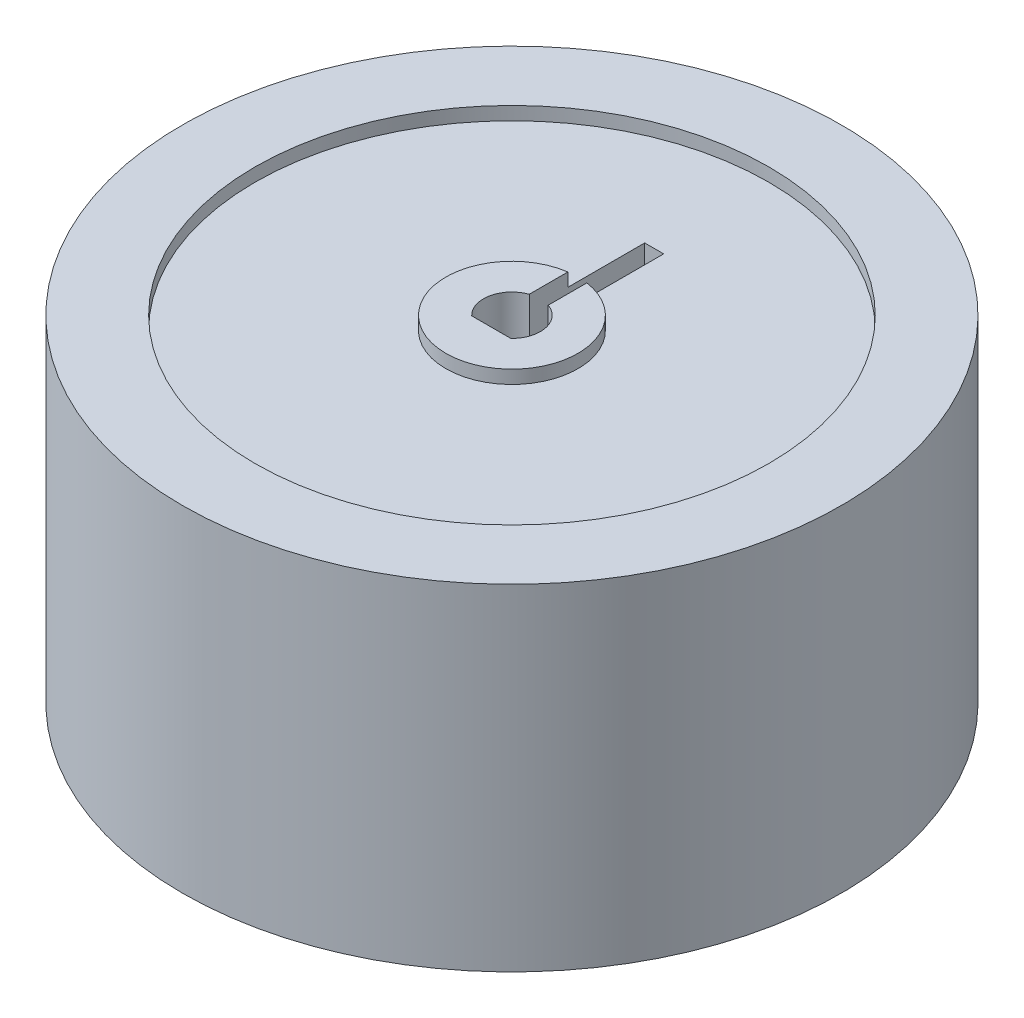
SolidWorks part; units mm, degrees
ref_plane "Front Plane" through (0, 0, 0) normal (0, 0, 1) x (1, 0, 0)
ref_plane "Top Plane" through (0, 0, 0) normal (0, 1, 0) x (1, 0, 0)
ref_plane "Right Plane" through (0, 0, 0) normal (1, 0, 0) x (0, 0, -1)
sketch "Sketch1" plane through (0, 0, 0) normal (0, 1, 0) x (1, 0, 0)
  circle A1 centre (0, 0) radius 17.375
extrude "Boss-Extrude1" add sketch "Sketch1" along normal blind 17.7
sketch "Sketch3" plane through (0, 17.7, 0) normal (0, 1, 0) x (1, 0, 0)
  line L0 (0, 17.375) -> (0, 13.545) construction
  circle A0 centre (0, 0) radius 17.375 construction
  circle A1 centre (0, 0) radius 13.545
extrude "Cut-Extrude1" cut sketch "Sketch3" against normal blind 0.7
sketch "Sketch4" plane through (0, 17, 0) normal (0, 1, 0) x (1, 0, 0)
  line L0 (0, 13.545) -> (0, 3.485) construction
  circle A0 centre (0, 0) radius 13.545 construction
  circle A1 centre (0, 0) radius 13.545 construction
  circle A2 centre (0, 0) radius 3.485
extrude "Boss-Extrude2" add sketch "Sketch4" along normal blind 0.7
sketch "Sketch5" plane through (0, 17.7, 0) normal (0, 1, 0) x (1, 0, 0)
  line L0 (-1.0305, -1.09) -> (1.0305, -1.09)
  arc A1 (-1.0305, -1.09) -> (1.0305, -1.09) centre (0, 0) cw
extrude "Cut-Extrude2" cut sketch "Sketch5" against normal up to surface (17.7 mm away) up to face at (0, 0, 17.375)
sketch "Sketch6" plane through (0, 17.7, 0) normal (0, 1, 0) x (1, 0, 0)
  line L1 (0, 7.5) -> (-0.5, 7.5) construction
  line L2 (-0.5, 7.5) -> (-0.5, 1.4142) construction
  line L3 (0, 7.5) -> (0.5, 7.5) construction
  line L4 (0.5, 7.5) -> (0.5, 1.4142) construction
  line L5 (-0.5, 7.5) -> (0.5, 7.5)
  line L6 (-0.5, 7.5) -> (-0.5, 1.4142)
  line L7 (-0.5, 1.4142) -> (0.5, 1.4142)
  line L8 (0.5, 7.5) -> (0.5, 1.4142)
  arc A0 (1.0305, -1.09) -> (-1.0305, -1.09) centre (0, 0) ccw construction
extrude "Cut-Extrude3" cut sketch "Sketch6" against normal up to surface (17.7 mm away) up to face at (0, 0, -0.205)
